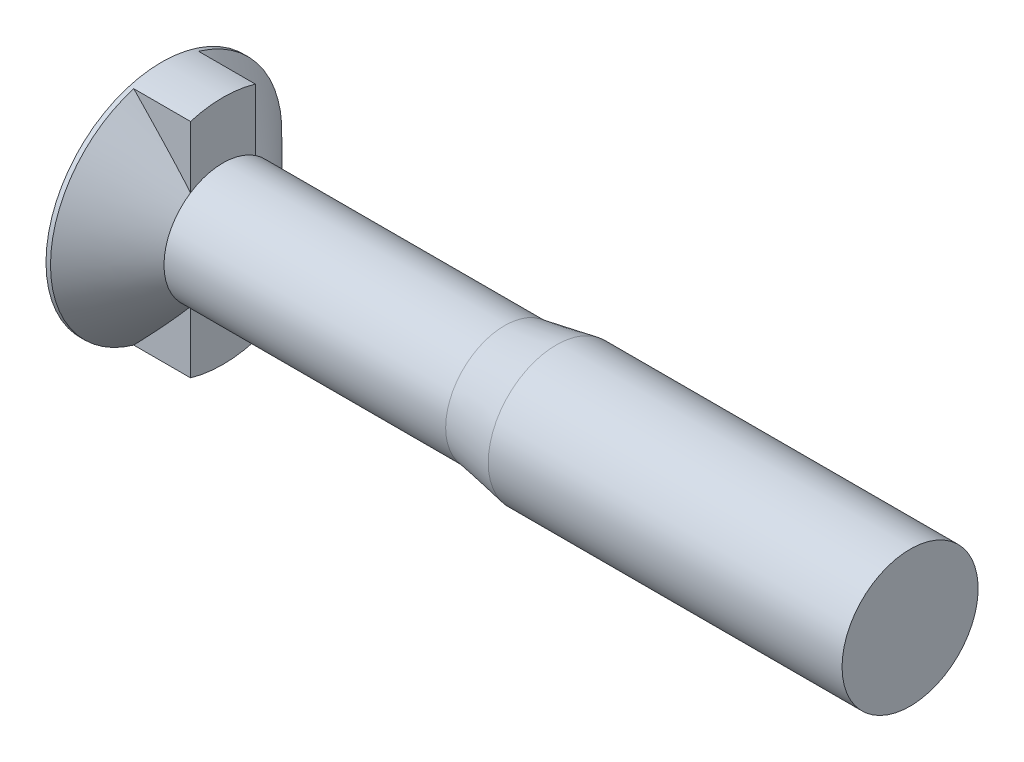
SolidWorks part; units mm, degrees
ref_plane "Front" through (0, 0, 0) normal (0, 0, 1) x (1, 0, 0)
ref_plane "Top" through (0, 0, 0) normal (0, 1, 0) x (1, 0, 0)
ref_plane "Right" through (0, 0, 0) normal (1, 0, 0) x (0, 0, -1)
sketch "Sketch2" plane through (0, 0, 0) normal (0, 0, 1) x (1, 0, 0)
  line L0 (-4.9405, 0) -> (36.2951, 0) construction
  line L1 (0, 0) -> (0, 8.5)
  line L2 (0, 8.5) -> (0.33, 8.5)
  line L3 (0.33, 8.5) -> (4.5, 4.33)
  line L4 (4.5, 4.33) -> (25.2, 4.33)
  line L5 (55, 5) -> (55, 0)
  line L6 (55, 0) -> (0, 0)
  line L7 (25.2, 4.33) -> (29, 5)
  line L8 (29, 5) -> (55, 5)
  dimension "D1" = 45
  dimension "d" = 10
  dimension "D2" = 10
revolve "Base" add sketch "Sketch2" angle 360 about L0
cosmetic thread "ThreadCosmetic1" [suppressed] parameters "D2"=7.5512
sketch "Sketch3" plane through (0, 0, 0) normal (0, 0, 1) x (1, 0, 0)
  line L0 (-0.9415, 0) -> (6.8139, 0) construction
  line L2 (0, 8.5) -> (4.5, 8.5)
  line L4 (4.5, 8.5) -> (4.5, -8.5)
  line L5 (4.5, -8.5) -> (0, -8.5)
  line L6 (0, -8.5) -> (0, 8.5)
  line L8 (0, 8.5) -> (0, -8.5) construction
  dimension "D1" = 17
  dimension "D2" = 4.5
extrude "Nib" add sketch "Sketch3" along normal mid plane 4.76
sketch "Sketch4" plane through (0, 0, 0) normal (-1, 0, 0) x (0, 0, 1)
  circle A0 centre (0, 0) radius 8.5 construction
  circle A1 centre (0, 0) radius 8.5
extrude "Cut-Extrude1" cut sketch "Sketch4" against normal through all flip side to cut
sketch "Sketch5" plane through (0, 0, 0) normal (0, 0, 1) x (1, 0, 0)
  line L0 (54.3878, 6.2244) -> (55.6122, 6.2244)
  line L1 (55.6122, 6.2244) -> (55.6122, 5)
  line L2 (55.6122, 5) -> (55, 3.9396)
  line L3 (54.3878, 5) -> (55, 3.9396)
  line L4 (54.3878, 6.2244) -> (54.3878, 5)
  line L5 (55, 0) -> (0, 0) construction
  line L6 (54.3878, 5) -> (55.6122, 5) construction
  line L7 (55, 5) -> (55, 3.9396) construction
  line L9 (55, 5) -> (29, 5) construction
  line L10 (55, -5) -> (55, 5) construction
  point P5 (55, 6.2244)
  dimension "D2" = 1.2244
revolve "Cut-Revolve10" [suppressed] cut sketch "Sketch5" angle 360 about L5
pattern_linear "LPattern10" [suppressed] count 18 spacing 1.4693 along (-1, 0, 0) of bodies 104
equation "\"D1@Sketch3\" = \"dk@Sketch2\""
equation "\"D2@Sketch3\" = \"k@Sketch2\""
equation "\"D2@Sketch5\" =  ( \"d@Sketch2\" - \"D2@ThreadCosmetic1\" )  / 2"
equation "\"D3@LPattern10\" = \"D2@Sketch5\" * 1.2"
equation "\"D1@LPattern10\" = \"b@Sketch2\" / \"D3@LPattern10\""
